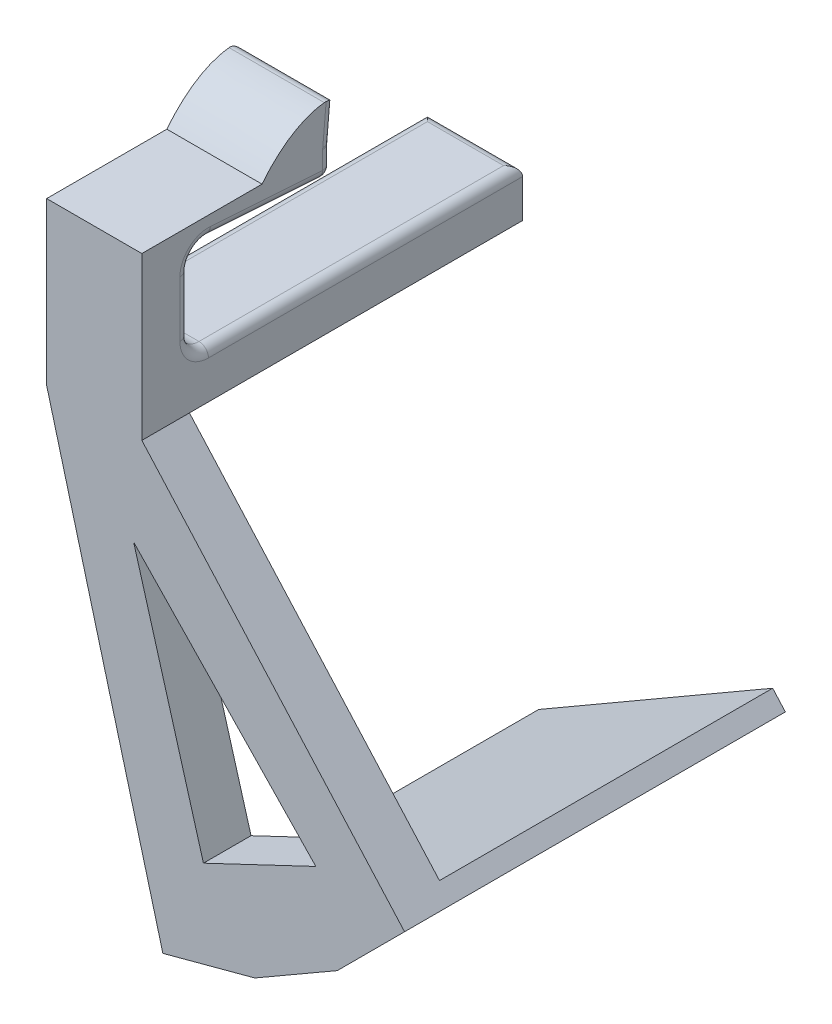
SolidWorks part; units mm, degrees
ref_plane "Front Plane" through (0, 0, 0) normal (0, 0, 1) x (1, 0, 0)
ref_plane "Top Plane" through (0, 0, 0) normal (0, 1, 0) x (1, 0, 0)
ref_plane "Right Plane" through (0, 0, 0) normal (1, 0, 0) x (0, 0, -1)
sketch "Sketch2" plane through (0, 0, 0) normal (1, 0, 0) x (0, 0, -1)
  line L0 (20, 17) -> (20.3636, 21.1559)
  line L1 (0, 0) -> (5, 0)
  line L2 (0, 0) -> (0, 17)
  line L3 (0, 17) -> (5, 17)
  line L4 (5, 0) -> (5, 17)
  line L6 (5, 0) -> (5, 7)
  line L9 (5, 17) -> (20, 17)
  line L10 (5, 17) -> (5, 15)
  line L11 (5, 15) -> (20, 15) construction
  line L12 (20, 17) -> (20, 15)
  line L13 (5, 5) -> (40, 5)
  line L14 (5, 5) -> (5, 0)
  line L15 (5, 0) -> (40, 0)
  line L16 (40, 5) -> (40, 0)
  line L20 (12.6252, 17) -> (20, 17)
  line L23 (20, 15) -> (20, 15.0689)
  line L24 (18.9335, 14.0711) -> (5, 15)
  arc A1 (20, 15.0689) -> (18.9335, 14.0711) centre (19, 15.0689) cw
  spline S0 degree 3 poles (12.6252, 17) (14.3903, 19.2591) (17.233, 21.4298) (20.3636, 21.1559) knots 0 0 0 0 1 1 1 1
  point P17 (15.7844, 19.9063)
  point P18 (0, 0)
  point P20 (21.2713, 20.9734)
  point P25 (20, 14)
  dimension "D12" = 1
  dimension "D2" = 85
  dimension "D6" = 10
  dimension "D7" = 2
  dimension "D8" = 5
  dimension "D9" = 15
  dimension "D10" = 35
  dimension "D11" = 1
extrude "Boss-Extrude1" add sketch "Sketch2" along normal blind 10 contours L1 L4 L3 L2 | L4 | L16 L13 L4 L15 | L12 L9 L4 L11 | L9 L0 | L11 L24 A1 L23 region at (0, 18.7287, -17.3002) region at (0, 15.7432, -12.9546) region at (0, 8.5, -2.5) region at (0, 2.5, -22.5)
sketch "Sketch4" plane through (0, 0, 0) normal (0, 0, 1) x (1, 0, 0)
  line L0 (10, 0) -> (-2.2086, -45.5631)
  line L1 (-2.2086, -45.5631) -> (-11.8678, -42.9749)
  line L2 (-11.8678, -42.9749) -> (-20.5281, -37.9749)
  line L3 (-20.5281, -37.9749) -> (-27.5992, -30.9038)
  line L4 (-27.5992, -30.9038) -> (0, 0)
  line L6 (0, 0) -> (10, 0)
  line L7 (10, 0) -> (0, 0) construction
  line L8 (10, 5) -> (-3.4586, -45.2281) construction
  line L9 (10, 5) -> (0, 5) construction
  line L10 (10, 0) -> (10, 17) construction
  line L11 (-18.2774, -29.6218) -> (-6.4709, -35.2264)
  line L12 (-6.4709, -35.2264) -> (0.8649, -9.6768)
  line L13 (0.8649, -9.6768) -> (-18.2774, -29.6218)
  dimension "D1" = 15
  dimension "D2" = 165
  dimension "D3" = 165
  dimension "D4" = 10
  dimension "D5" = 52
extrude "Boss-Extrude2" add sketch "Sketch4" against normal up to surface (5 mm away) up to face at (5, 10, -5)
sketch "Sketch5" plane through (0, 0, -5) normal (0, 0, -1) x (-1, 0, 0)
  line L0 (2.2086, -45.5631) -> (11.8678, -42.9749)
  line L1 (11.8678, -42.9749) -> (20.5281, -37.9749)
  line L2 (20.5281, -37.9749) -> (27.5992, -30.9038)
  line L3 (27.5992, -30.9038) -> (26.267, -29.4121)
  line L4 (27.5992, -30.9038) -> (0, 0) construction
  line L5 (26.267, -29.4121) -> (1.691, -43.6312)
  line L6 (-10, 0) -> (2.2086, -45.5631) construction
  line L7 (1.691, -43.6312) -> (2.2086, -45.5631)
  dimension "D1" = 2
extrude "Boss-Extrude3" add sketch "Sketch5" along normal blind 35
fillet "Fillet1" radius 2 2 edges at (5, 5, -5) (5, 15, -5)
fillet "Fillet2" radius 1 19 edges at (0, 14.3386, -19.6832) (10, 14.3386, -19.6832) (0, 14.3227, -5.6336) (0, 9.9311, -5) (0, 5.5858, -5.5858) (0, 14.4644, -13.0333) (0, 5, -23.5) (5, 5, -40) (10, 5, -23.5) (10, 5.5858, -5.5858) (10, 9.9311, -5) (10, 14.3227, -5.6336) (10, 14.4644, -13.0333) (0, 19.078, -20.1818) (10, 19.078, -20.1818) (5, 21.1559, -20.3636) (10, 16.0344, -20) (0, 16.0344, -20) (5, 17, -20)
ref_plane "Plane1" through (5, 0, 0) normal (1, 0, 0) x (0, 0, -1)
mirror "Mirror2" about plane through (5, 0, 0) normal (1, 0, 0) of "Boss-Extrude3", "Boss-Extrude2"
sketch "Sketch6" plane through (0, 0, -5) normal (0, 0, -1) x (-1, 0, 0)
  line L0 (0, 0) -> (-12.2086, -45.5631)
  line L1 (-5, -18.6603) -> (-11.691, -43.6312) construction
  line L2 (-12.2086, -45.5631) -> (1.179, -62.7339)
  line L3 (1.179, -62.7339) -> (43.8323, -23.3566)
  line L4 (43.8323, -23.3566) -> (0, 0)
  line M3 (-11.691, -43.6312) -> (-5, -18.6603)
  line M4 (-5, -18.6603) -> (1.691, -43.6312)
  line M5 (1.691, -43.6312) -> (26.267, -29.4121)
  line M6 (26.267, -29.4121) -> (0, 0)
  line M11 (18.2774, -29.6218) -> (6.4709, -35.2264)
  line M12 (6.4709, -35.2264) -> (-0.8649, -9.6768)
  line M13 (-0.8649, -9.6768) -> (18.2774, -29.6218)
extrude "Cut-Extrude1" cut sketch "Sketch6" against normal through all contours L3 L4 L0 L2 M6 M5 M4 M3 | L0 M6 M4 M5 M13 M11 M12 | M11 M13 M12 region at (-12.7331, -15.0636, -5) region at (-21.5205, -12.4207, -5) region at (-7.9611, -24.8416, -5)
delete or keep bodies "Body-Delete/Keep 1" type delete bodies bodies 108
